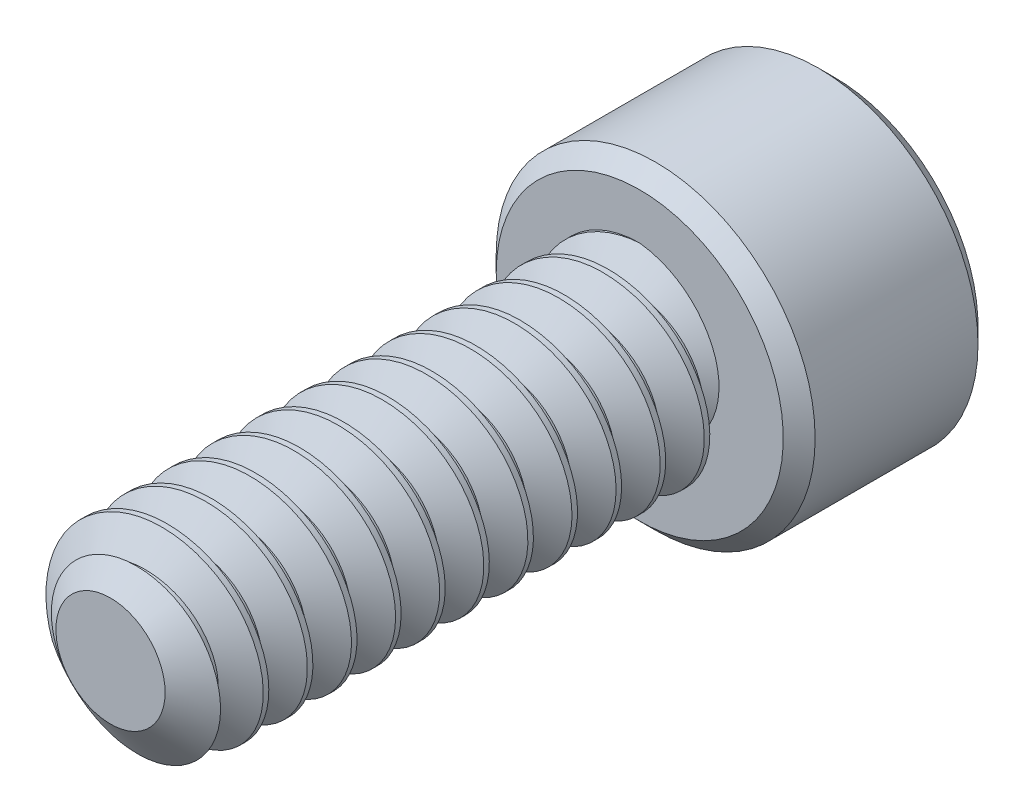
SolidWorks part; units mm, degrees
note: '?' marks a value the reader was unsure of.
other "DetailItem1"
ref_plane "Front Plane" through (0, 0, 0) normal (0, 0, 1) x (1, 0, 0)
ref_plane "Top Plane" through (0, 0, 0) normal (0, 1, 0) x (1, 0, 0)
ref_plane "Right Plane" through (0, 0, 0) normal (1, 0, 0) x (0, 0, -1)
sketch "Sketch1" plane through (0, 0, 0) normal (0, 0, 1) x (1, 0, 0)
  circle A0 centre (0, 0) radius 1.7526
  dimension "OD" = 3.5052
extrude "Extrude1" add sketch "Sketch1" against normal blind 9.525
sketch "Sketch2" plane through (0, 0, 0) normal (0, 0, 1) x (1, 0, 0)
  circle A0 centre (0, 0) radius 1.7526 construction
  circle A1 centre (0, 0) radius 1.7526
curve "Helix/Spiral1" pitch 0.7937 height 10.3188 turns 13 parameters "pitch"=0.7937
sketch "Sketch3" plane through (0, 0, 0) normal (1, 0, 0) x (0, 0, -1)
  line L0 (-0.6945, 1.7526) -> (-0.3969, 1.237)
  line L1 (-0.3969, 1.237) -> (-0.2977, 1.237)
  line L2 (-0.2977, 1.237) -> (0, 1.7526)
  line L3 (-0.6945, 1.7526) -> (0, 1.7526)
  line L4 (-0.3473, 1.7526) -> (-0.3473, 1.237) construction
  line L5 (-0.5457, 1.4948) -> (-0.1488, 1.4948) construction
  line L6 (0, 1.7526) -> (0, -1.7526) construction
  dimension "D1" = 0.0992
  dimension "D2" = 0.3969
  dimension "D3" = 60
sweep "Cut-Sweep1" cut profiles "Sketch3" path "Helix/Spiral1"
sketch "Sketch4" plane through (0, 0, 0) normal (1, 0, 0) x (0, 0, -1)
  line L0 (0.5388, 1.7526) -> (0, 0.983)
  line L1 (0, 0.983) -> (0, 1.7526)
  line L2 (0.5388, 1.7526) -> (0, 1.7526)
  line L3 (-0.6945, 1.7526) -> (0, 1.7526) construction
  line L4 (0, 0) -> (7.0209, 0) construction
  dimension "D1" = 55
  dimension "D2" = 0.254
revolve "Cut-Revolve1" cut sketch "Sketch4" angle 360 about L4
sketch "Sketch6" plane through (0, 0, -9.525) normal (0, 0, -1) x (-1, 0, 0)
  circle A0 centre (0, 0) radius 2.8702
  dimension "head dia" = 5.7404
extrude "Extrude2" add sketch "Sketch6" along normal blind 3.5052
sketch "Sketch7" plane through (0, 0, -13.0302) normal (0, 0, -1) x (-1, 0, 0)
  line L1 (0, 1.604) -> (-1.3891, 0.802)
  line L2 (-1.3891, 0.802) -> (-1.3891, -0.802)
  line L3 (-1.3891, -0.802) -> (0, -1.604)
  line L4 (0, -1.604) -> (1.3891, -0.802)
  line L5 (1.3891, -0.802) -> (1.3891, 0.802)
  line L6 (1.3891, 0.802) -> (0, 1.604)
  circle A0 centre (0, 0) radius 1.3891 construction
  dimension "hex dia" = 2.7781
extrude "Cut-Extrude1" cut sketch "Sketch7" against normal blind 2.0836
sketch "Sketch8" plane through (0, 0, -13.0302) normal (0, 0, -1) x (-1, 0, 0)
  circle A0 centre (0, 0) radius 1.604
extrude "Cut-Extrude2" cut sketch "Sketch8" against normal through all draft 45
chamfer "Chamfer1" distance 0.287 angle 45 2 edges at (-2.8702, 0, -13.0302) (-2.8702, 0, -9.525)
sketch "Sketch10" plane through (0, 0, -9.525) normal (0, 0, 1) x (1, 0, 0)
  circle A1 centre (0, 0) radius 1.7526
  circle A2 centre (0, 0) radius 1.7526
  dimension "D1" = 0
ref_plane "Plane1" through (0, 0, -31.75) normal (0, 0, 1) x (1, 0, 0)
extrude "partial thread" [suppressed] add sketch "Sketch10" along normal up to surface (12.7 mm away) separate body
chamfer "Chamfer2" [suppressed] distance 0.0701 angle 45
combine bodies "Combine1" [suppressed] operation type? add bodies to combine 107 108
sketch "Sketch9" plane through (0, 0, 0) normal (1, 0, 0) x (0, 0, -1)
  line L0 (0, 1.7526) -> (0, -1.7526) construction
  line L1 (1.9844, 1.7526) -> (1.9844, -1.7526) construction
  dimension "D1" = 1.9844
equation "\"D3@Helix/Spiral1\" = \"screw length@Extrude1\"+\"pitch@Helix/Spiral1\""
equation "\"D1@Sketch3\" = \"pitch@Helix/Spiral1\"*.125"
equation "\"D2@Sketch3\" = \"pitch@Helix/Spiral1\"*.5"
equation "\"D1@Cut-Extrude1\" = \"hex dia@Sketch7\"*.75"
equation "\"D1@Chamfer1\" = \"head dia@Sketch6\"*.05"
equation "\"D1@Sketch9\" = \"pitch@Helix/Spiral1\"*2.5"
equation "\"D1@Chamfer2\"=\"OD@Sketch1\"*.02"
